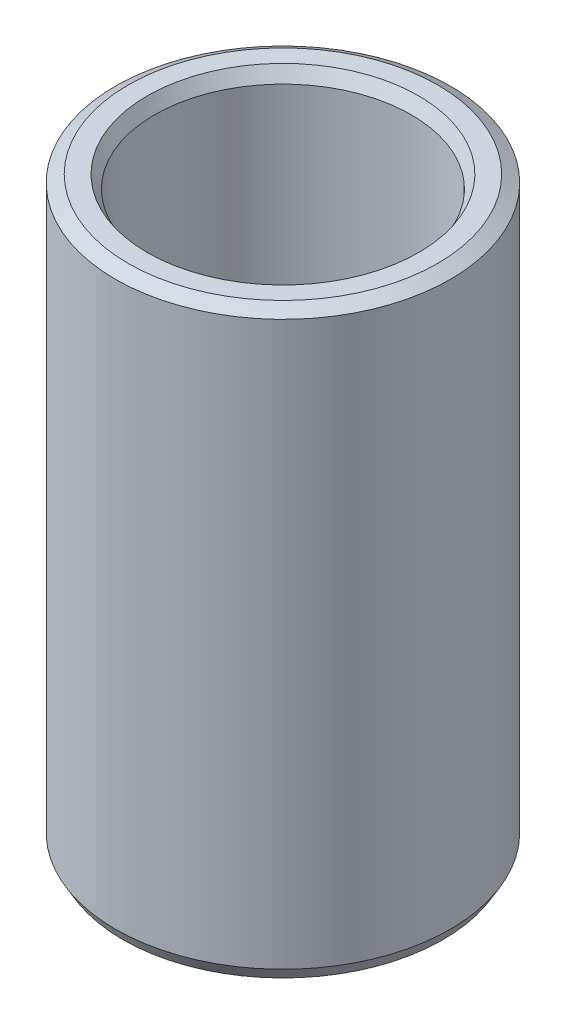
SolidWorks part; units mm, degrees
ref_plane "Front Plane" through (0, 0, 0) normal (0, 0, 1) x (1, 0, 0)
ref_plane "Top Plane" through (0, 0, 0) normal (0, 1, 0) x (1, 0, 0)
ref_plane "Right Plane" through (0, 0, 0) normal (1, 0, 0) x (0, 0, -1)
sketch "Sketch1" plane through (0, 0, 0) normal (0, 1, 0) x (1, 0, 0)
  circle A0 centre (0, 0) radius 27.5
  dimension "SLEEVE_OD" = 55
extrude "Boss-Extrude1" add sketch "Sketch1" along normal blind 95.7551
sketch "Sketch2" plane through (0, 0, 0) normal (0, 1, 0) x (1, 0, 0)
  circle A0 centre (0, 0) radius 21.0891
  dimension "BORE_D" = 42.1782
extrude "Cut-Extrude1" cut sketch "Sketch2" along normal through all
chamfer "Chamfer1" distance 1.2078 angle 60 4 edges at (0, 95.7551, 21.0891) (0, 0, 21.0891) (0, 0, 27.5) (0, 95.7551, 27.5) first distance on face at (0, 95.7551, 21.0891) first distance on face at (0, 0, 21.0891) first distance on face at (0, 95.7551, 27.5)
